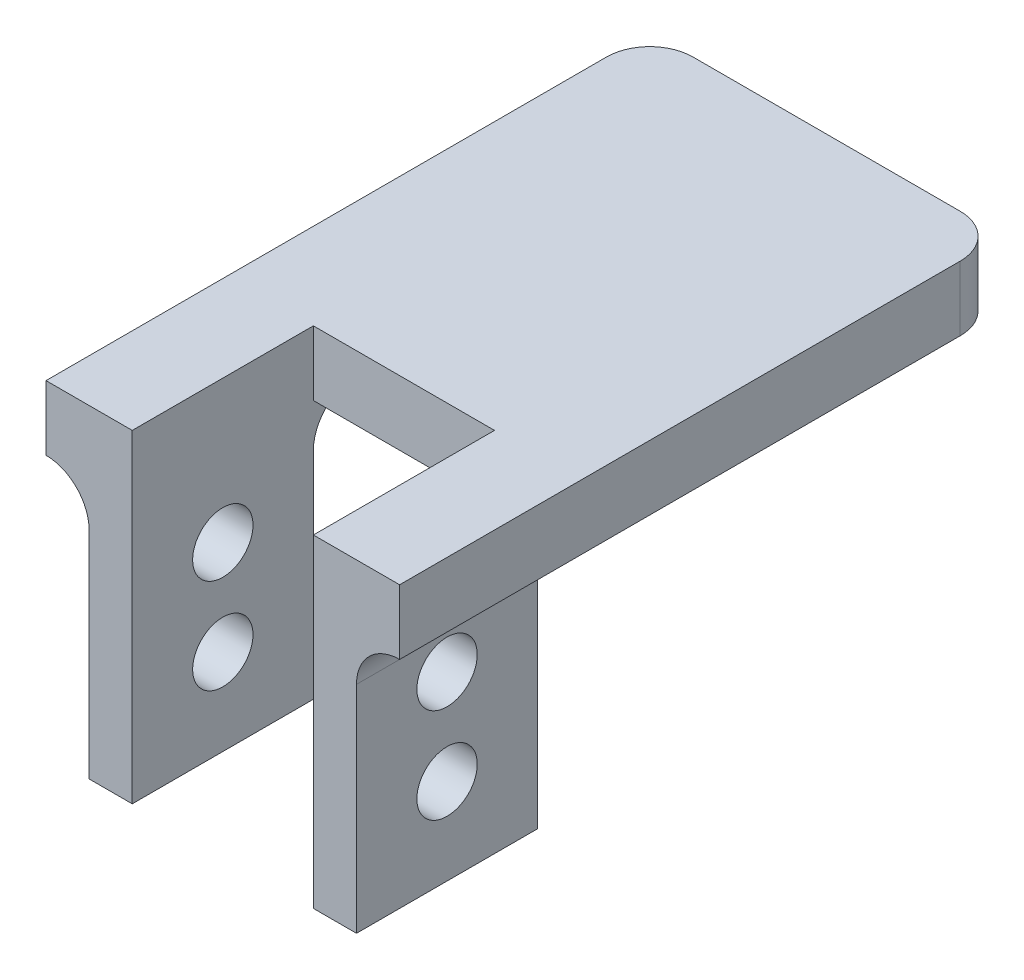
SolidWorks part; units mm, degrees
ref_plane "Front Plane" through (0, 0, 0) normal (0, 0, 1) x (1, 0, 0)
ref_plane "Top Plane" through (0, 0, 0) normal (0, 1, 0) x (1, 0, 0)
ref_plane "Right Plane" through (0, 0, 0) normal (1, 0, 0) x (0, 0, -1)
sketch "Sketch1" plane through (0, 0, 0) normal (0, 1, 0) x (1, 0, 0)
  line L0 (-20.5, -10.5) -> (-10.5, -10.5)
  line L1 (-10.5, -10.5) -> (-10.5, 10.5)
  line L2 (-10.5, 10.5) -> (10.5, 10.5)
  line L3 (10.5, 10.5) -> (10.5, -10.5)
  line L4 (10.5, -10.5) -> (20.5, -10.5)
  line L5 (20.5, -10.5) -> (20.5, 59.5)
  line L6 (20.5, 59.5) -> (-20.5, 59.5)
  line L7 (-20.5, 59.5) -> (-20.5, -10.5)
  point P11 (0, 59.5)
  point P13 (10.5, 0)
  dimension "D2" = 21
  dimension "D3" = 21
  dimension "D4" = 21
  dimension "D5" = 10
  dimension "D6" = 70
extrude "Boss-Extrude1" add sketch "Sketch1" along normal blind 7.5
sketch "Sketch2" plane through (0, 0, 0) normal (0, -1, 0) x (1, 0, 0)
  line L1 (-15.5, 10.5) -> (-10.5, 10.5)
  line L2 (-15.5, 10.5) -> (-15.5, -10.5)
  line L3 (-15.5, -10.5) -> (-10.5, -10.5)
  line L4 (-10.5, 10.5) -> (-10.5, -10.5)
  line L5 (15.5, 10.5) -> (10.5, 10.5)
  line L6 (15.5, 10.5) -> (15.5, -10.5)
  line L7 (15.5, -10.5) -> (10.5, -10.5)
  line L8 (10.5, 10.5) -> (10.5, -10.5)
  dimension "D1" = 5
extrude "Boss-Extrude2" add sketch "Sketch2" along normal blind 30
sketch "Sketch3" plane through (20.5, 0, 0) normal (1, 0, 0) x (0, 0, -1)
  line L0 (10.5, -30) -> (-10.5, -30) construction
  circle A0 centre (0, -9) radius 3.5
  circle A1 centre (0, -20) radius 3.5
  point P6 (0, -30)
  dimension "D1" = 7
  dimension "D2" = 7
  dimension "D3" = 11
  dimension "D4" = 10
extrude "Cut-Extrude1" cut sketch "Sketch3" against normal through all
fillet "Fillet1" radius 5 6 edges at (-20.5, 3.75, -59.5) (20.5, 3.75, -59.5) (-13, 0, -10.5) (13, 0, -10.5) (-15.5, 0, 0) (15.5, 0, 0)
